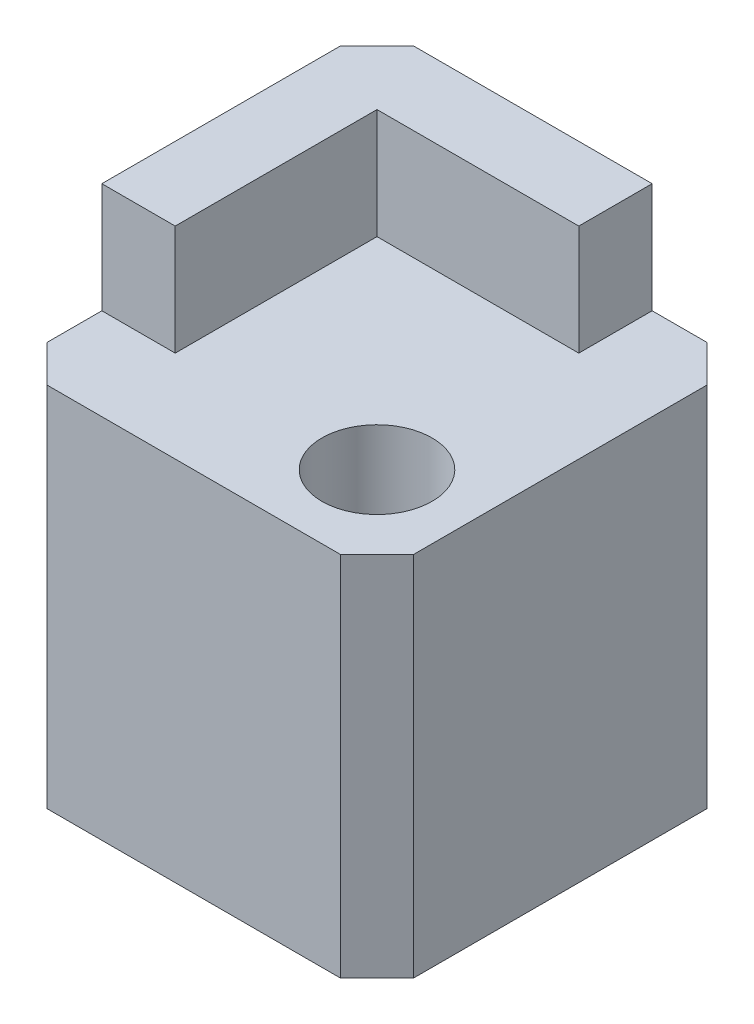
SolidWorks part; units mm, degrees
ref_plane "Front Plane" through (0, 0, 0) normal (0, 0, 1) x (1, 0, 0)
ref_plane "Top Plane" through (0, 0, 0) normal (0, 1, 0) x (1, 0, 0)
ref_plane "Right Plane" through (0, 0, 0) normal (1, 0, 0) x (0, 0, -1)
sketch "Sketch1" plane through (0, 0, 0) normal (0, 1, 0) x (1, 0, 0)
  line L0 (0, 5.5) -> (-5.5, 5.5)
  line L1 (-5.5, 5.5) -> (-5.5, 0)
  line L2 (-5.5, 0) -> (-7.5, 0)
  line L3 (-7.5, 0) -> (-7.5, 7.5)
  line L4 (-7.5, 7.5) -> (0, 7.5)
  line L5 (0, 7.5) -> (0, 5.5)
  line L7 (-7.5, 7.5) -> (2.5, 7.5)
  line L8 (-7.5, 7.5) -> (-7.5, -2.5)
  line L9 (-7.5, -2.5) -> (2.5, -2.5)
  line L10 (2.5, 7.5) -> (2.5, -2.5)
  circle A0 centre (0, 0) radius 1.5
  dimension "D1" = 3
  dimension "D2" = 5.5
  dimension "D3" = 5.5
  dimension "D4" = 2
  dimension "D5" = 10
extrude "Boss-Extrude1" add sketch "Sketch1" against normal blind 10 contours L7 L10 L9 L8
extrude "Boss-Extrude2" add sketch "Sketch1<3>" along normal blind 3 contours L5 L4 L3 L2 L1 L0 region at (-2.75, 0, -5.6061)
sketch "Sketch1<3>" plane through (0, 0, 0) normal (0, 1, 0) x (1, 0, 0) same geometry as "Sketch1"
chamfer "Chamfer1" distance 1 angle 45 4 edges at (-7.5, -3.5, -7.5) (2.5, -5, -7.5) (-7.5, -5, 2.5) (2.5, -5, 2.5)
extrude "Cut-Extrude1" cut sketch "Sketch1<4>" against normal through all contours A0 region at (0, 0, 0)
sketch "Sketch1<4>" plane through (0, 0, 0) normal (0, 1, 0) x (1, 0, 0) same geometry as "Sketch1"
cosmetic thread "Cosmetic Thread1" parameters "D2"=4
